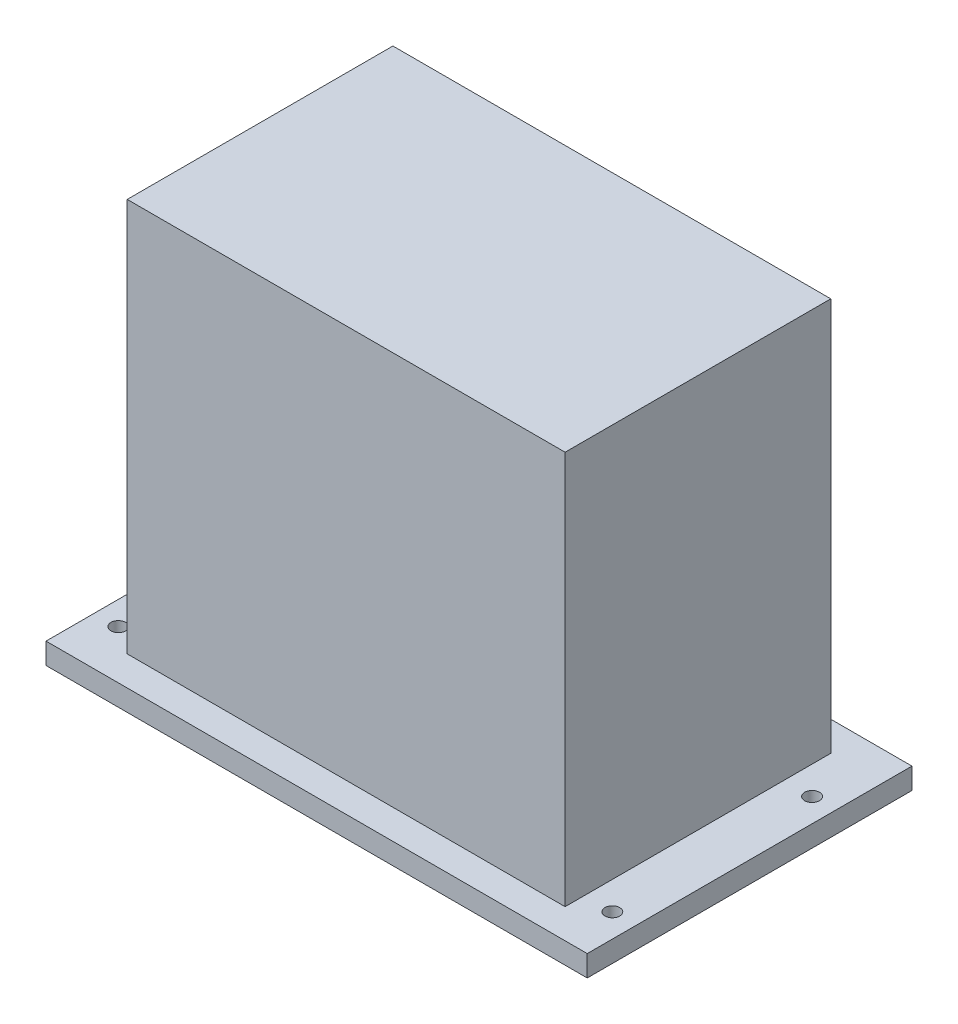
SolidWorks part; units mm, degrees
ref_plane "Front Plane" through (0, 0, 0) normal (0, 0, 1) x (1, 0, 0)
ref_plane "Top Plane" through (0, 0, 0) normal (0, 1, 0) x (1, 0, 0)
ref_plane "Right Plane" through (0, 0, 0) normal (1, 0, 0) x (0, 0, -1)
sketch "Sketch1" plane through (0, 0, 0) normal (0, 1, 0) x (1, 0, 0)
  line L0 (-35.5, 33) -> (-15.5, 33)
  line L1 (-55, -33) -> (55, -33)
  line L2 (-55, -33) -> (-55, 33)
  line L3 (-55, 33) -> (55, 33)
  line L4 (55, -33) -> (55, 33)
  line L5 (-55, -33) -> (55, 33) construction
  line L6 (-55, 33) -> (55, -33) construction
  line L7 (-35.5, 33) -> (-35.5, 27)
  line L8 (-15.5, 33) -> (-15.5, 27)
  line L9 (-35.5, 27) -> (-15.5, 27)
  line L10 (0, -55) -> (0, 55) construction
  line L11 (15.5, 33) -> (15.5, 27)
  line L12 (35.5, 27) -> (15.5, 27)
  line L13 (35.5, 33) -> (35.5, 27)
  line L14 (35.5, 33) -> (15.5, 33)
  circle A0 centre (50.2, 17.5) radius 1.5
  circle A1 centre (50.2, -23.1) radius 1.5
  circle A2 centre (42.2, 24.5) radius 1.5
  circle A5 centre (42.2, -24.2) radius 1.5
  circle A6 centre (-42.2, 24.5) radius 1.5
  circle A7 centre (-50.2, 17.5) radius 1.5
  circle A10 centre (-50.2, -23.1) radius 1.5
  circle A11 centre (-42.2, -24.2) radius 1.5
  point P0 (0, 0)
  point P20 (42.2, 24.5)
  point P29 (42.2, 18.5)
  point P30 (0, 0)
  dimension "D6" = 3
  dimension "D9" = 9.9
  dimension "D13" = 8.8
  dimension "D1" = 66
  dimension "D2" = 110
  dimension "D3" = 6
  dimension "D4" = 20
  dimension "D5" = 19.5
  dimension "D7" = 4.8
  dimension "D8" = 15.5
  dimension "D10" = 8.5
  dimension "D11" = 8
  dimension "D14" = 4.8
extrude "Boss-Extrude1" add sketch "Sketch1" along normal blind 4.3 contours L3 L13 L12 L11 L8 L9 L7 L2 L1 L4 A10 A6 A5 A2 A1 A0 A7 A11 region at (0, 0, 1.0232)
sketch "Sketch2" plane through (0, 4.3, 0) normal (0, 1, 0) x (1, 0, 0)
  line L1 (-44.5, -27) -> (44.5, -27)
  line L2 (-44.5, -27) -> (-44.5, 27)
  line L3 (-44.5, 27) -> (44.5, 27)
  line L4 (44.5, -27) -> (44.5, 27)
  line L5 (-44.5, -27) -> (44.5, 27) construction
  line L6 (-44.5, 27) -> (44.5, -27) construction
  point P0 (0, 0)
  dimension "D1" = 89
  dimension "D2" = 54
extrude "Boss-Extrude2" add sketch "Sketch2" along normal blind 80
